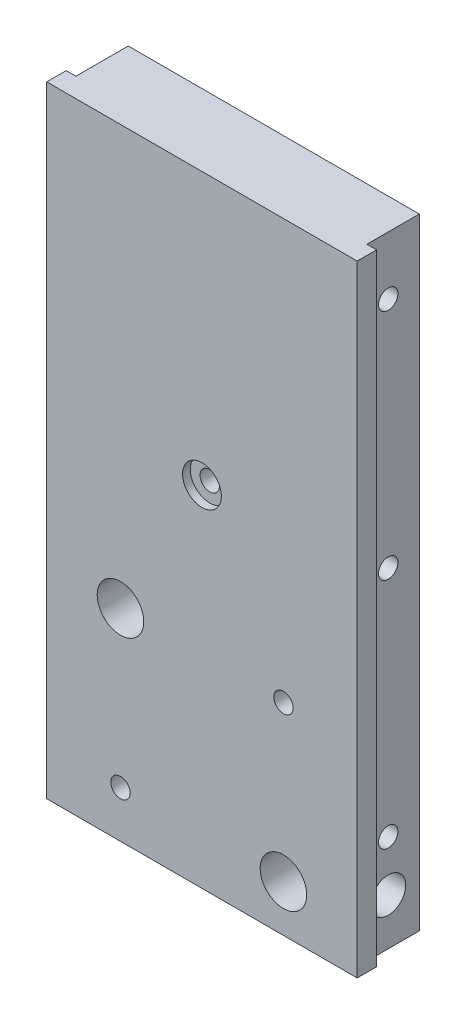
SolidWorks part; units mm, degrees
ref_plane "Front Plane" through (0, 0, 0) normal (0, 0, 1) x (1, 0, 0)
ref_plane "Top Plane" through (0, 0, 0) normal (0, 1, 0) x (1, 0, 0)
ref_plane "Right Plane" through (0, 0, 0) normal (1, 0, 0) x (0, 0, -1)
sketch "Sketch1" plane through (0, 0, 0) normal (0, 1, 0) x (1, 0, 0)
  line L0 (-16.0793, 0) -> (63.9207, 0)
  line L1 (63.9207, 0) -> (63.9207, 5)
  line L2 (63.9207, 5) -> (61.4207, 5)
  line L3 (61.4207, 5) -> (61.4207, 18.5)
  line L4 (61.4207, 18.5) -> (-13.5793, 18.5)
  line L5 (-13.5793, 18.5) -> (-13.5793, 5)
  line L6 (-13.5793, 5) -> (-16.0793, 5)
  line L7 (-16.0793, 5) -> (-16.0793, 0)
  point P7 (0, 0)
  point P10 (23.9207, 0)
  point P11 (23.9207, 18.5)
  dimension "D1" = 18.5
  dimension "D2" = 75
  dimension "D3" = 80
  dimension "D4" = 13.5
extrude "Boss-Extrude1" add sketch "Sketch1" along normal blind 160
sketch "Sketch2" plane through (0, 0, 0) normal (0, 0, 1) x (1, 0, 0)
  line L0 (-16.0793, 160) -> (63.9207, 160) construction
  circle A0 centre (23.9207, 90) radius 5
  point P4 (23.9207, 160)
  dimension "D2" = 10
  dimension "D1" = 70
extrude "Cut-Extrude1" cut sketch "Sketch2" against normal blind 2
sketch "Sketch3" plane through (0, 0, -2) normal (0, 0, 1) x (1, 0, 0)
  circle A0 centre (23.9207, 90) radius 2.5
  dimension "D1" = 5
extrude "Cut-Extrude2" cut sketch "Sketch3" against normal through all
sketch "Sketch4" plane through (0, 0, 0) normal (0, 0, 1) x (1, 0, 0)
  line L1 (2.9207, 12) -> (44.9207, 12)
  line L2 (2.9207, 12) -> (2.9207, 52)
  line L3 (2.9207, 52) -> (44.9207, 52)
  line L4 (44.9207, 12) -> (44.9207, 52)
  line L5 (-16.0793, 0) -> (63.9207, 0) construction
  circle A0 centre (2.9207, 52) radius 6
  circle A1 centre (44.9207, 12) radius 6
  circle A2 centre (2.9207, 12) radius 2.5
  circle A3 centre (44.9207, 52) radius 2.5
  point P6 (23.9207, 0)
  point P7 (23.9207, 12)
  dimension "D4" = 5
  dimension "D5" = 5
  dimension "D6" = 12
  dimension "D7" = 12
  dimension "D1" = 42
  dimension "D2" = 40
  dimension "D3" = 12
extrude "Cut-Extrude3" cut sketch "Sketch4" against normal through all contours L3 A0 L2 | L2 A0 L3 | A3 | A2 | A1 region at (2.0719, 52.8488, 0) region at (5.4672, 49.4535, 0)
sketch "Sketch5" plane through (0, 0, 0) normal (0, -1, 0) x (1, 0, 0)
  line L0 (-13.5793, -18.5) -> (-13.5793, -5) construction
  line L1 (61.4207, -5) -> (61.4207, -18.5) construction
  circle A0 centre (57.9207, -11.7164) radius 2.5
  circle A1 centre (-10.0793, -11.7164) radius 2.5
  point P4 (0, 0)
  dimension "D1" = 5
  dimension "D2" = 3.5
  dimension "D3" = 3.5
extrude "Cut-Extrude4" cut sketch "Sketch5" against normal blind 5
sketch "Sketch6" plane through (61.4207, 0, 0) normal (1, 0, 0) x (0, 0, -1)
  line L0 (18.5, 160) -> (18.5, 0) construction
  line L1 (5, 160) -> (18.5, 160) construction
  line L2 (5, 0) -> (18.5, 0) construction
  circle A0 centre (10.5, 145) radius 2.5
  circle A1 centre (10.5, 85) radius 2.5
  circle A2 centre (10.5, 25) radius 2.5
  circle A3 centre (10.5, 12) radius 4.5
  point P10 (0, 0)
  point P11 (11, 12.1891)
  dimension "D1" = 5
  dimension "D3" = 9
  dimension "D2" = 8
  dimension "D4" = 60
  dimension "D5" = 60
  dimension "D6" = 12
  dimension "D7" = 15
extrude "Cut-Extrude5" cut sketch "Sketch6" against normal blind 15
sketch "Sketch7" plane through (-13.5793, 0, 0) normal (-1, 0, 0) x (0, 0, 1)
  line L0 (-18.5, 160) -> (-5, 160) construction
  line L1 (-18.5, 160) -> (-18.5, 0) construction
  line L2 (-18.5, 0) -> (-5, 0) construction
  circle A0 centre (-10.5, 145) radius 2.5
  circle A1 centre (-10.5, 85) radius 2.5
  circle A2 centre (-10.5, 25) radius 2.5
  circle A3 centre (-10.5, 52) radius 3.517
  point P12 (0, 0)
  point P13 (-14, 50.4908)
  dimension "D1" = 5
  dimension "D2" = 15
  dimension "D3" = 8
  dimension "D4" = 60
  dimension "D5" = 60
  dimension "D6" = 52
  dimension "D7" = 8
extrude "Cut-Extrude6" cut sketch "Sketch7" against normal blind 15
